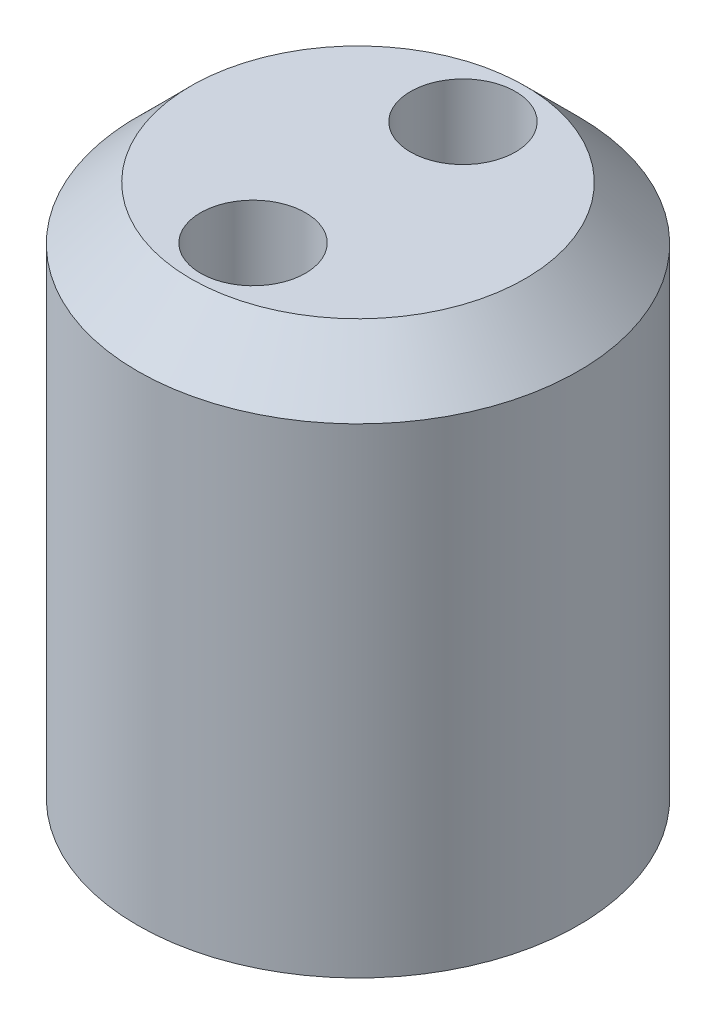
SolidWorks part; units mm, degrees
ref_plane "Front Plane" through (0, 0, 0) normal (0, 0, 1) x (1, 0, 0)
ref_plane "Top Plane" through (0, 0, 0) normal (0, 1, 0) x (1, 0, 0)
ref_plane "Right Plane" through (0, 0, 0) normal (1, 0, 0) x (0, 0, -1)
sketch "Sketch1" plane through (0, 0, 0) normal (0, 1, 0) x (1, 0, 0)
  line L0 (0, -5) -> (0, 5) construction
  circle A0 centre (0, 0) radius 10.5
  circle A2 centre (0, 5) radius 2.5
  circle A3 centre (0, -5) radius 2.5
  dimension "D1" = 21
  dimension "D2" = 5
  dimension "D3" = 10
extrude "Boss-Extrude1" add sketch "Sketch1" along normal blind 25.4
chamfer "Chamfer1" distance 2.54 angle 45 1 edges at (0, 25.4, 10.5)
equation "\"cf_tube_outer_diameter\" = 25mm"
equation "\"cf_tube_inner_diameter\" = 21mm"
equation "\"mid_plate_mid_to_top\" = 100mm"
equation "\"mid_plate_mid_to_bottom\" = 100mm"
equation "\"mid_plate_horizontal_spacing\" = 250mm"
equation "\"cf_plate_thickness\" = 4mm"
equation "\"mid_tube_length\" = 500mm"
equation "\"D1@Sketch1\"=\"cf_tube_inner_diameter\""
